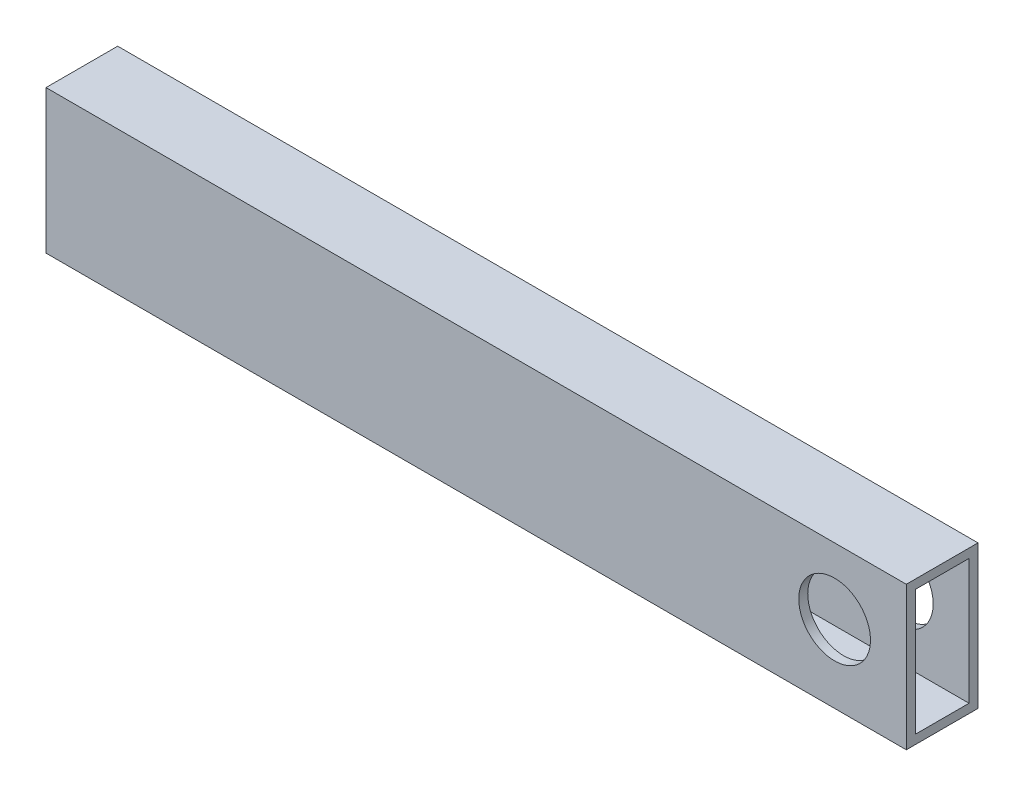
SolidWorks part; units mm, degrees
ref_plane "Front Plane" through (0, 0, 0) normal (0, 0, 1) x (1, 0, 0)
ref_plane "Top Plane" through (0, 0, 0) normal (0, 1, 0) x (1, 0, 0)
ref_plane "Right Plane" through (0, 0, 0) normal (1, 0, 0) x (0, 0, -1)
sketch "Sketch1" plane through (0, 0, 0) normal (1, 0, 0) x (0, 0, -1)
  line L1 (0, 0) -> (25.4, 0)
  line L2 (0, 0) -> (0, 50.8)
  line L3 (0, 50.8) -> (25.4, 50.8)
  line L4 (25.4, 0) -> (25.4, 50.8)
  line L5 (3.175, 47.625) -> (22.225, 47.625)
  line L6 (3.175, 47.625) -> (3.175, 3.175)
  line L7 (3.175, 3.175) -> (22.225, 3.175)
  line L8 (22.225, 47.625) -> (22.225, 3.175)
  dimension "D1" = 3.175
  dimension "D2" = 3.175
  dimension "D3" = 3.175
  dimension "D4" = 3.175
  dimension "D5" = 50.8
  dimension "D6" = 25.4
extrude "Boss-Extrude1" add sketch "Sketch1" along normal blind 304.8
sketch "Sketch2" plane through (0, 0, -25.4) normal (0, 0, -1) x (-1, 0, 0)
  line L0 (-304.8, 0) -> (-304.8, 50.8) construction
  circle A0 centre (-279.4, 27.2833) radius 12.7
  dimension "D2" = 25.4
  dimension "D1" = 25.4
extrude "Cut-Extrude1" cut sketch "Sketch2" against normal through all both and the other way through all
